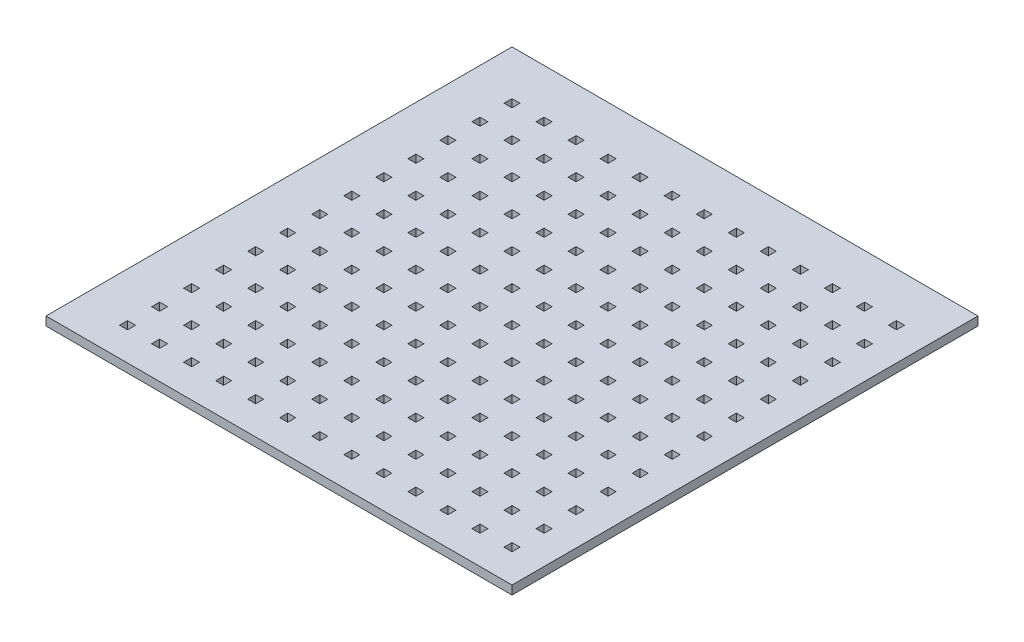
SolidWorks part; units mm, degrees
ref_plane "Front Plane" through (0, 0, 0) normal (0, 0, 1) x (1, 0, 0)
ref_plane "Top Plane" through (0, 0, 0) normal (0, 1, 0) x (1, 0, 0)
ref_plane "Right Plane" through (0, 0, 0) normal (1, 0, 0) x (0, 0, -1)
sketch "Sketch1" plane through (0, 0, 0) normal (0, 1, 0) x (1, 0, 0)
  line L1 (-80, -80) -> (80, -80)
  line L2 (-80, -80) -> (-80, 80)
  line L3 (-80, 80) -> (80, 80)
  line L4 (80, -80) -> (80, 80)
  line L5 (-80, -80) -> (80, 80) construction
  line L6 (-80, 80) -> (80, -80) construction
  point P0 (0, 0)
  dimension "D1" = 160
extrude "Boss-Extrude1" add sketch "Sketch1" along normal blind 3
sketch "Sketch2" plane through (0, 3, 0) normal (0, 1, 0) x (1, 0, 0)
  line L7 (1.38, -4.12) -> (4.12, -4.12)
  line L8 (1.38, -4.12) -> (1.38, -1.38)
  line L9 (1.38, -1.38) -> (4.12, -1.38)
  line L10 (4.12, -4.12) -> (4.12, -1.38)
  line L11 (1.38, -4.12) -> (4.12, -1.38) construction
  line L12 (1.38, -1.38) -> (4.12, -4.12) construction
  point P0 (2.75, -2.75)
  dimension "D1" = 2.74
  dimension "D2" = 2.75
  dimension "D3" = 2.75
extrude "Cut-Extrude1" cut sketch "Sketch2" against normal through all
pattern_linear "LPattern1" count 7 spacing 11 along (0, 0, 1) count 7 spacing 11 along (0, 0, -1) of "Cut-Extrude1"
pattern_linear "LPattern2" count 7 spacing 11 along (1, 0, 0) count 7 spacing 11 along (-1, 0, 0) of "LPattern1", "Cut-Extrude1"
